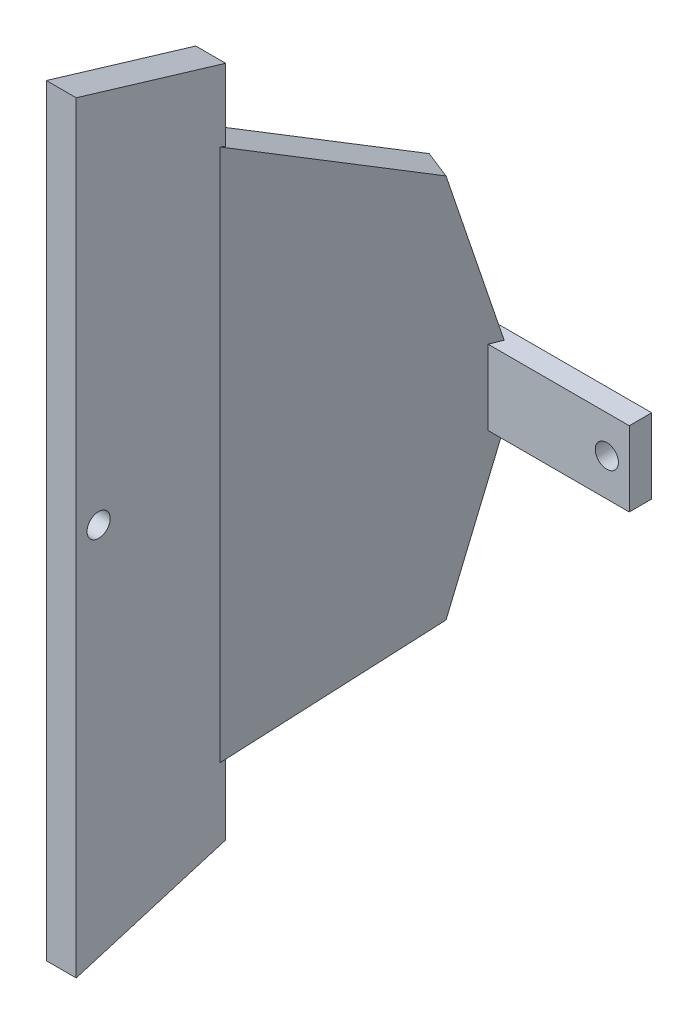
SolidWorks part; units mm, degrees
ref_plane "前视基准面" through (0, 0, 0) normal (0, 0, 1) x (1, 0, 0)
ref_plane "上视基准面" through (0, 0, 0) normal (0, 1, 0) x (1, 0, 0)
ref_plane "右视基准面" through (0, 0, 0) normal (1, 0, 0) x (0, 0, -1)
other "Configuration Table"
sketch "草图1" plane through (0, 0, 0) normal (0, 1, 0) x (1, 0, 0)
  line L0 (0, 0) -> (3, 0)
  line L1 (3, 0) -> (3, 16.697)
  line L2 (3, 16.697) -> (14.119, 45)
  line L3 (14.119, 45) -> (33, 45)
  line L4 (33, 45) -> (33, 48)
  line L5 (33, 48) -> (11, 48)
  line L6 (11, 48) -> (0, 20)
  line L7 (0, 20) -> (0, 0)
  dimension "D1" = 20
  dimension "D2" = 28
  dimension "D3" = 11
  dimension "D4" = 22
  dimension "D5" = 3
  dimension "D6" = 3
  dimension "D7" = 4
extrude "凸台-拉伸1" add sketch "草图1" along normal blind 10
sketch "草图2" plane through (0, 0, 0) normal (-1, 0, 0) x (0, 0, 1)
  line L0 (0, 5) -> (-3, 5)
  line L2 (0, 10) -> (0, 0) construction
  circle A1 centre (-3, 5) radius 1.55
  dimension "D2" = 3.1
  dimension "D1" = 3
extrude "切除-拉伸3" cut sketch "草图2" against normal blind 10 contours A1
sketch "草图3" plane through (0, 0, -48) normal (0, 0, -1) x (-1, 0, 0)
  line L0 (-33, 5) -> (-30, 5)
  line L1 (-33, 10) -> (-33, 0) construction
  circle A0 centre (-30, 5) radius 1.55
  dimension "D2" = 3.1
  dimension "D1" = 3
extrude "切除-拉伸4" cut sketch "草图3" against normal blind 10 contours A0 region at (30, 3.4938, -48)
sketch "草图4" plane through (-6.8066, 0, -2.674) normal (-0.9308, 0, -0.3657) x (-0.3657, 0, 0.9308)
  line L0 (-18.615, 10) -> (-18.615, 41)
  line L1 (-18.615, 41) -> (-42.6982, 30.73)
  line L3 (-42.6982, 30.73) -> (-48.6982, 10)
  line L6 (-42.6982, -20.73) -> (-18.615, -31)
  line L7 (-18.615, -31) -> (-18.615, 10)
  line L8 (-48.6982, 0) -> (-42.6982, -20.73)
  line L9 (-48.6982, 10) -> (-48.6982, 0)
  point P16 (-48.6982, 0)
  dimension "D1" = 6
  dimension "D2" = 6
  dimension "D3" = 31
  dimension "D4" = 31
  dimension "D5" = 20.73
  dimension "D6" = 20.73
extrude "凸台-拉伸2" add sketch "草图4" against normal blind 4
sketch "草图5" plane through (0, 0, 0) normal (-1, 0, 0) x (0, 0, 1)
  line L0 (-20, -31) -> (-20, -40)
  line L1 (-20, -40) -> (0, -46)
  line L2 (0, -46) -> (0, 56)
  line L4 (-20, 41) -> (-20, -40)
  line L5 (-20, 41) -> (-20, 50)
  line L6 (-20, 50) -> (0, 56)
  line L7 (0, 10) -> (0, 0) construction
  point P7 (-9.1535, 62.1101)
  point P8 (-2.6514, -49.8344)
  point P10 (-10.3456, -55.3612)
  point P15 (0, 0)
  circle M1 centre (-3, 5) radius 1.55
  dimension "D1" = 9
  dimension "D2" = 9
  dimension "D3" = 46
  dimension "D4" = 46
extrude "凸台-拉伸4" add sketch "草图5" against normal blind 4 contours M1 | L4 L5 L6 L2 L1 region at (0, 5, -3)
